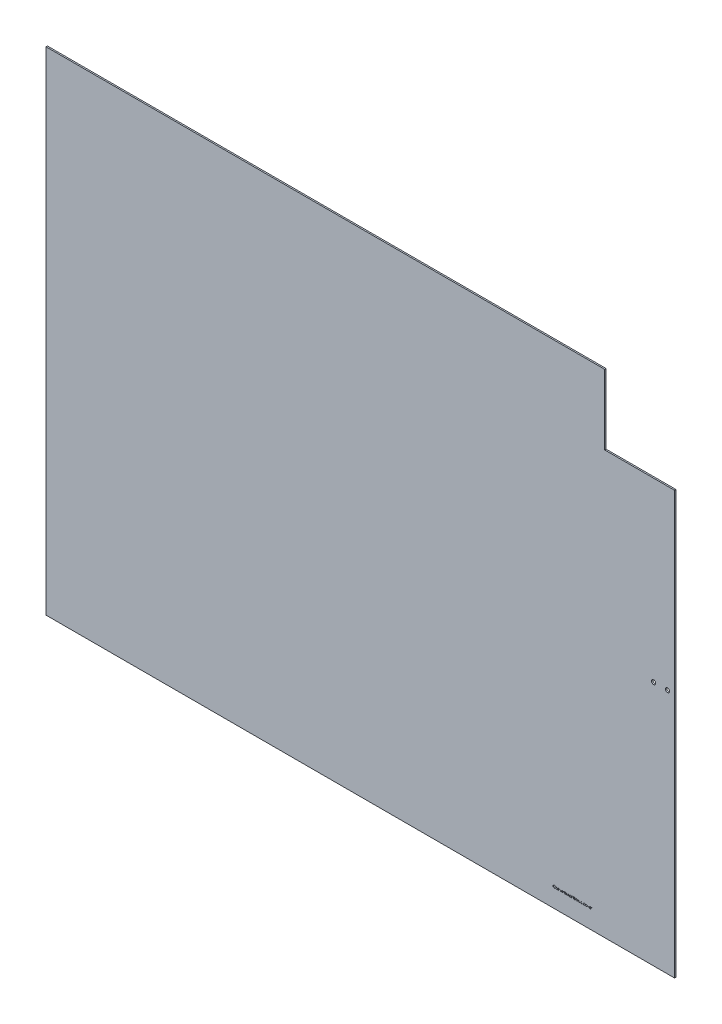
SolidWorks part; units mm, degrees
ref_plane "Front Plane" through (0, 0, 0) normal (0, 0, 1) x (1, 0, 0)
ref_plane "Top Plane" through (0, 0, 0) normal (0, 1, 0) x (1, 0, 0)
ref_plane "Right Plane" through (0, 0, 0) normal (1, 0, 0) x (0, 0, -1)
sketch "Sketch1" plane through (0, 0, 0) normal (0, 0, 1) x (1, 0, 0)
  line L1 (0, 0) -> (900, 0)
  line L2 (0, 0) -> (0, 705)
  line L3 (0, 705) -> (900, 705)
  line L4 (900, 0) -> (900, 705)
  dimension "D1" = 900
  dimension "D2" = 705
extrude "Boss-Extrude1" add sketch "Sketch1" along normal blind 2
sketch "Sketch2" plane through (0, 0, 2) normal (0, 0, 1) x (1, 0, 0)
  line L1 (900, 705) -> (800, 705)
  line L2 (900, 705) -> (900, 605)
  line L3 (900, 605) -> (800, 605)
  line L4 (800, 705) -> (800, 605)
  dimension "D1" = 100
  dimension "D2" = 100
extrude "Cut-Extrude1" cut sketch "Sketch2" against normal through all
sketch "Sketch3" plane through (0, 0, 2) normal (0, 0, 1) x (1, 0, 0)
  line L0 (725.7837, 25.5822) -> (873.0501, 25.5822) construction
  line L1 (729.4632, 28.4399) -> (729.1883, 28.2296)
  line L2 (729.1883, 26.4347) -> (729.4632, 26.2265)
  line L3 (733.2773, 28.1399) -> (733.5914, 28.1399)
  line L4 (733.5914, 28.1399) -> (733.5914, 27.6953)
  line L5 (737.0914, 26.9676) -> (737.0914, 25.5822)
  line L6 (737.0914, 25.5822) -> (736.7773, 25.5822)
  line L7 (736.7773, 25.5822) -> (736.7773, 26.969)
  line L8 (735.3414, 26.5771) -> (735.3414, 25.5822)
  line L9 (735.3414, 25.5822) -> (735.0273, 25.5822)
  line L10 (735.0273, 25.5822) -> (735.0273, 26.8827)
  line L11 (733.5914, 26.6584) -> (733.5914, 25.5822)
  line L12 (733.5914, 25.5822) -> (733.2773, 25.5822)
  line L13 (733.2773, 25.5822) -> (733.2773, 28.1399)
  line L14 (737.8093, 28.1399) -> (738.1234, 28.1399)
  line L15 (738.1234, 28.1399) -> (738.1234, 27.6666)
  line L16 (738.1234, 26.0456) -> (738.1234, 24.6399)
  line L17 (738.1234, 24.6399) -> (737.8093, 24.6399)
  line L18 (737.8093, 24.6399) -> (737.8093, 28.1399)
  line L19 (741.0401, 28.1399) -> (741.3542, 28.1399)
  line L20 (741.3542, 28.1399) -> (741.3542, 27.7633)
  line L21 (742.2516, 28.0971) -> (742.0791, 27.825)
  line L22 (741.3542, 26.4417) -> (741.3542, 25.5822)
  line L23 (741.3542, 25.5822) -> (741.0401, 25.5822)
  line L24 (741.0401, 25.5822) -> (741.0401, 28.1399)
  line L25 (744.6649, 26.3899) -> (744.9439, 26.2433)
  line L26 (745.0785, 26.7937) -> (742.7901, 26.7937)
  line L27 (742.823, 27.1078) -> (744.7644, 27.1078)
  line L28 (746.9183, 27.8208) -> (746.7051, 27.6014)
  line L29 (745.4824, 25.8836) -> (745.6906, 26.1206)
  line L30 (748.8029, 27.8208) -> (748.5898, 27.6014)
  line L31 (747.367, 25.8836) -> (747.5752, 26.1206)
  line L32 (752.5721, 28.1399) -> (752.8862, 28.1399)
  line L33 (752.8862, 28.1399) -> (752.8862, 27.7633)
  line L34 (753.7837, 28.0971) -> (753.6112, 27.825)
  line L35 (752.8862, 26.4417) -> (752.8862, 25.5822)
  line L36 (752.8862, 25.5822) -> (752.5721, 25.5822)
  line L37 (752.5721, 25.5822) -> (752.5721, 28.1399)
  line L38 (755.4439, 25.5822) -> (755.4439, 29.1719)
  line L39 (755.4439, 29.1719) -> (755.758, 29.1719)
  line L40 (755.758, 29.1719) -> (755.758, 27.6757)
  line L41 (755.758, 26.0554) -> (755.758, 25.5822)
  line L42 (755.758, 25.5822) -> (755.4439, 25.5822)
  line L43 (761.367, 28.1399) -> (761.367, 25.5822)
  line L44 (761.367, 25.5822) -> (761.0529, 25.5822)
  line L45 (761.0529, 25.5822) -> (761.0529, 26.0246)
  line L46 (761.0529, 27.6666) -> (761.0529, 28.1399)
  line L47 (761.0529, 28.1399) -> (761.367, 28.1399)
  line L48 (764.5978, 27.5853) -> (764.3348, 27.4219)
  line L49 (764.3348, 26.3001) -> (764.5978, 26.1276)
  line L50 (765.226, 29.1719) -> (765.5401, 29.1719)
  line L51 (765.5401, 29.1719) -> (765.5401, 27.0966)
  line L52 (765.5401, 27.0966) -> (766.7039, 28.1399)
  line L53 (766.7039, 28.1399) -> (767.1555, 28.1399)
  line L54 (767.1555, 28.1399) -> (765.8051, 26.9283)
  line L55 (765.8051, 26.9283) -> (767.2901, 25.5822)
  line L56 (767.2901, 25.5822) -> (766.8393, 25.5822)
  line L57 (766.8393, 25.5822) -> (765.5401, 26.7607)
  line L58 (765.5401, 26.7607) -> (765.5401, 25.5822)
  line L59 (765.5401, 25.5822) -> (765.226, 25.5822)
  line L60 (765.226, 25.5822) -> (765.226, 29.1719)
  line L61 (771.508, 27.5853) -> (771.2451, 27.4219)
  line L62 (771.2451, 26.3001) -> (771.508, 26.1276)
  line L63 (775.0529, 28.1399) -> (775.3929, 28.1399)
  line L64 (775.3929, 28.1399) -> (776.242, 26.2777)
  line L65 (776.242, 26.2777) -> (777.0911, 28.1399)
  line L66 (777.0911, 28.1399) -> (777.4311, 28.1399)
  line L67 (777.4311, 28.1399) -> (776.2644, 25.5822)
  line L68 (776.2644, 25.5822) -> (776.2196, 25.5822)
  line L69 (776.2196, 25.5822) -> (775.0529, 28.1399)
  line L70 (780.0687, 26.3899) -> (780.3478, 26.2433)
  line L71 (780.4824, 26.7937) -> (778.1939, 26.7937)
  line L72 (778.2269, 27.1078) -> (780.1683, 27.1078)
  line L73 (781.0208, 28.1399) -> (781.3349, 28.1399)
  line L74 (781.3349, 28.1399) -> (781.3349, 27.7633)
  line L75 (782.2324, 28.0971) -> (782.0599, 27.825)
  line L76 (781.3349, 26.4417) -> (781.3349, 25.5822)
  line L77 (781.3349, 25.5822) -> (781.0208, 25.5822)
  line L78 (781.0208, 25.5822) -> (781.0208, 28.1399)
  spline S0 degree 3 poles (729.1883, 28.2296) (729.1501, 28.2766) (729.0894, 28.3438) (729.0018, 28.4256) (728.9339, 28.4829) (728.8621, 28.5343) (728.7883, 28.5826) (728.7111, 28.6258) (728.6043, 28.6783) (728.4647, 28.733) (728.2272, 28.7954) (728.0416, 28.8135) (727.9165, 28.8129) knots 0 0 0 0 0.125475 0.187121 0.248294 0.309295 0.36985 0.430973 0.492456 0.616148 0.740844 1 1 1 1
  spline S1 degree 3 poles (727.9165, 28.8129) (727.8466, 28.8138) (727.7426, 28.8063) (727.6062, 28.7862) (727.5065, 28.7641) (727.4089, 28.7361) (727.3128, 28.7027) (727.2196, 28.6613) (727.128, 28.6156) (727.0402, 28.564) (726.9571, 28.5077) (726.8791, 28.4473) (726.8061, 28.3827) (726.7379, 28.314) (726.6751, 28.2406) (726.6179, 28.1628) (726.5652, 28.0815) (726.518, 27.9969) (726.4784, 27.9089) (726.4434, 27.8188) (726.4157, 27.7256) (726.3938, 27.6301) (726.3733, 27.4979) (726.3661, 27.3969) (726.367, 27.3287) knots 0 0 0 0 0.087502 0.130463 0.172752 0.215403 0.25765 0.300153 0.343121 0.385925 0.427686 0.468818 0.509492 0.549883 0.58998 0.630405 0.670869 0.711384 0.751627 0.791776 0.832459 0.873319 0.914543 1 1 1 1
  spline S2 degree 3 poles (726.367, 27.3287) (726.3665, 27.2271) (726.3807, 27.077) (726.4263, 26.8841) (726.4765, 26.7487) (726.5384, 26.6188) (726.6167, 26.4965) (726.7073, 26.3801) (726.8116, 26.2723) (726.926, 26.1738) (727.0487, 26.087) (727.1795, 26.0147) (727.3169, 25.9545) (727.4619, 25.9083) (727.6686, 25.8639) (727.8292, 25.8505) (727.9382, 25.8514) knots 0 0 0 0 0.12629 0.186726 0.246146 0.305576 0.365429 0.426326 0.48884 0.551725 0.613919 0.675484 0.737334 0.800229 0.864502 1 1 1 1
  spline S3 degree 3 poles (727.9382, 25.8514) (728.0584, 25.8514) (728.2369, 25.8683) (728.4648, 25.9303) (728.6261, 25.9941) (728.7794, 26.0772) (728.977, 26.2135) (729.1076, 26.3419) (729.1883, 26.4347) knots 0 0 0 0 0.252949 0.374755 0.49594 0.617181 0.740909 1 1 1 1
  spline S4 degree 3 poles (729.4632, 26.2265) (729.4198, 26.1689) (729.351, 26.0863) (729.2502, 25.9852) (729.1705, 25.9151) (729.0874, 25.849) (728.9993, 25.7887) (728.9075, 25.7334) (728.8121, 25.6827) (728.7134, 25.6378) (728.6114, 25.5994) (728.5065, 25.5662) (728.3989, 25.539) (728.2881, 25.5177) (728.1353, 25.4984) (728.0188, 25.4918) (727.9403, 25.4924) knots 0 0 0 0 0.123053 0.183475 0.243727 0.304279 0.364863 0.425946 0.487391 0.54922 0.611144 0.673529 0.736961 0.800785 0.866013 1 1 1 1
  spline S5 degree 3 poles (727.9403, 25.4924) (727.8658, 25.4915) (727.7558, 25.4975) (727.6113, 25.5131) (727.5076, 25.5303) (727.4064, 25.5506) (727.3089, 25.5779) (727.2139, 25.6084) (727.122, 25.6443) (727.0329, 25.6849) (726.947, 25.7307) (726.8644, 25.7813) (726.7842, 25.8358) (726.7076, 25.8958) (726.6087, 25.9824) (726.5398, 26.0538) (726.4967, 26.1045) knots 0 0 0 0 0.13775 0.203917 0.26878 0.332414 0.394754 0.45618 0.516996 0.577396 0.637198 0.696999 0.756756 0.816554 0.876948 1 1 1 1
  spline S6 degree 3 poles (726.4967, 26.1045) (726.4242, 26.1892) (726.3267, 26.325) (726.2236, 26.5214) (726.1612, 26.6748) (726.1125, 26.8348) (726.0665, 27.0603) (726.0525, 27.2346) (726.0529, 27.3525) knots 0 0 0 0 0.247156 0.36878 0.490734 0.613614 0.738958 1 1 1 1
  spline S7 degree 3 poles (726.0529, 27.3525) (726.0528, 27.4763) (726.0685, 27.6598) (726.1254, 27.8952) (726.1847, 28.0614) (726.26, 28.2206) (726.3531, 28.3714) (726.4627, 28.5149) (726.5882, 28.6489) (726.7257, 28.7715) (726.8731, 28.8793) (727.0298, 28.969) (727.1944, 29.044) (727.3678, 29.1016) (727.6144, 29.1565) (727.8063, 29.1717) (727.9361, 29.1719) knots 0 0 0 0 0.127014 0.187955 0.248014 0.307748 0.368235 0.42947 0.492743 0.556258 0.618217 0.679655 0.741246 0.803415 0.866815 1 1 1 1
  spline S8 degree 3 poles (727.9361, 29.1719) (728.0157, 29.1721) (728.1338, 29.1666) (728.2883, 29.1456) (728.3999, 29.1245) (728.5091, 29.0983) (728.6149, 29.0642) (728.718, 29.0251) (728.8177, 28.9802) (728.9136, 28.9297) (729.0057, 28.8743) (729.0931, 28.814) (729.1766, 28.7493) (729.2547, 28.6789) (729.355, 28.5798) (729.421, 28.4967) (729.4632, 28.4399) knots 0 0 0 0 0.135683 0.201215 0.265682 0.329267 0.392395 0.45507 0.517127 0.57879 0.63974 0.700192 0.759806 0.819628 0.879355 1 1 1 1
  spline S9 degree 3 poles (731.3267, 28.1847) (731.4208, 28.1857) (731.56, 28.1721) (731.7382, 28.1275) (731.864, 28.0823) (731.9823, 28.0216) (732.1347, 27.924) (732.2363, 27.8313) (732.2985, 27.7633) knots 0 0 0 0 0.258332 0.382134 0.503804 0.624693 0.746871 1 1 1 1
  spline S10 degree 3 poles (732.2985, 27.7633) (732.3555, 27.701) (732.4319, 27.6011) (732.5142, 27.4567) (732.5633, 27.3445) (732.6019, 27.2281) (732.6391, 27.0652) (732.6486, 26.9389) (732.649, 26.854) knots 0 0 0 0 0.253834 0.376506 0.498534 0.621368 0.744565 1 1 1 1
  spline S11 degree 3 poles (732.649, 26.854) (732.6496, 26.7684) (732.6378, 26.6413) (732.5992, 26.4769) (732.5584, 26.3591) (732.5061, 26.2452) (732.4422, 26.1358) (732.3663, 26.0306) (732.2803, 25.9306) (732.1852, 25.8384) (732.0821, 25.7581) (731.973, 25.6893) (731.8563, 25.6339) (731.7333, 25.5902) (731.5572, 25.5483) (731.4197, 25.5377) (731.3267, 25.5373) knots 0 0 0 0 0.123337 0.183265 0.243172 0.302898 0.363774 0.425605 0.489659 0.553785 0.616222 0.677854 0.739517 0.802097 0.865866 1 1 1 1
  spline S12 degree 3 poles (731.3267, 25.5373) (731.2333, 25.5377) (731.0953, 25.5482) (730.9188, 25.5902) (730.7956, 25.634) (730.6784, 25.6893) (730.5686, 25.7579) (730.4654, 25.8385) (730.3704, 25.9306) (730.2844, 26.0306) (730.2085, 26.1358) (730.1446, 26.2452) (730.0922, 26.3591) (730.0514, 26.4769) (730.0128, 26.6413) (730.0011, 26.7684) (730.0016, 26.854) knots 0 0 0 0 0.134635 0.198324 0.260825 0.322714 0.384555 0.446913 0.510958 0.574931 0.636685 0.697483 0.757134 0.816966 0.876818 1 1 1 1
  spline S13 degree 3 poles (730.0016, 26.854) (730.0021, 26.9387) (730.0117, 27.0647) (730.0487, 27.2272) (730.0874, 27.3431) (730.1369, 27.4549) (730.2181, 27.5996) (730.2958, 27.6987) (730.3522, 27.7612) knots 0 0 0 0 0.255238 0.378679 0.501088 0.622714 0.746241 1 1 1 1
  spline S14 degree 3 poles (730.3522, 27.7612) (730.4138, 27.8301) (730.5163, 27.9219) (730.6683, 28.0215) (730.788, 28.081) (730.9137, 28.1278) (731.0925, 28.1721) (731.2322, 28.1856) (731.3267, 28.1847) knots 0 0 0 0 0.252713 0.374819 0.496436 0.617911 0.741288 1 1 1 1
  spline S15 degree 3 poles (731.3253, 27.8706) (731.2583, 27.8704) (731.1588, 27.8614) (731.0308, 27.8303) (730.9394, 27.7977) (730.8518, 27.7556) (730.7679, 27.7039) (730.6874, 27.6433) (730.612, 27.5738) (730.5429, 27.4979) (730.4824, 27.4171) (730.431, 27.3326) (730.3881, 27.2443) (730.3562, 27.1514) (730.3248, 27.0212) (730.3159, 26.92) (730.3157, 26.8519) knots 0 0 0 0 0.126044 0.187165 0.247399 0.30838 0.36978 0.432584 0.497641 0.562401 0.625557 0.687332 0.748313 0.809791 0.871768 1 1 1 1
  spline S16 degree 3 poles (730.3157, 26.8519) (730.3159, 26.7632) (730.3315, 26.6299) (730.3899, 26.4619) (730.4484, 26.3423) (730.5218, 26.2316) (730.6083, 26.133) (730.707, 26.0478) (730.8166, 25.9771) (730.9349, 25.921) (731.1033, 25.8671) (731.236, 25.8504) (731.3253, 25.8514) knots 0 0 0 0 0.168179 0.251488 0.335841 0.419834 0.502345 0.583649 0.665931 0.748717 0.831047 1 1 1 1
  spline S17 degree 3 poles (731.3253, 25.8514) (731.4146, 25.8505) (731.5472, 25.8669) (731.7152, 25.9212) (731.8334, 25.977) (731.943, 26.048) (732.0424, 26.1325) (732.1281, 26.2319) (732.2014, 26.3425) (732.2609, 26.4617) (732.319, 26.6299) (732.3348, 26.7632) (732.3349, 26.8519) knots 0 0 0 0 0.168983 0.250908 0.333708 0.416005 0.49766 0.579893 0.663902 0.748466 0.831791 1 1 1 1
  spline S18 degree 3 poles (732.3349, 26.8519) (732.3348, 26.92) (732.3259, 27.0212) (732.2944, 27.1514) (732.2625, 27.2443) (732.2198, 27.3328) (732.1674, 27.4168) (732.1072, 27.4982) (732.0372, 27.5736) (731.9619, 27.6433) (731.8814, 27.7039) (731.7976, 27.7554) (731.7102, 27.7981) (731.6188, 27.83) (731.4912, 27.8616) (731.392, 27.8703) (731.3253, 27.8706) knots 0 0 0 0 0.128274 0.19027 0.251768 0.312769 0.374793 0.43797 0.503047 0.568125 0.63095 0.692369 0.752973 0.813641 0.874355 1 1 1 1
  spline S19 degree 3 poles (733.5914, 27.6953) (733.644, 27.7708) (733.7504, 27.9037) (733.8804, 28.0138) (733.9461, 28.055) knots 0 0 0 0 0.543395 1 1 1 1
  spline S20 degree 3 poles (733.9461, 28.055) (734.0277, 28.0971) (734.1995, 28.1638) (734.3827, 28.184) (734.4734, 28.1847) knots 0 0 0 0 0.503035 1 1 1 1
  spline S21 degree 3 poles (734.4734, 28.1847) (734.5344, 28.1839) (734.6261, 28.1762) (734.7438, 28.1449) (734.8285, 28.1125) (734.9082, 28.0732) (734.9813, 28.0272) (735.0469, 27.9755) (735.105, 27.9158) (735.1573, 27.8465) (735.225, 27.7327) (735.2638, 27.6356) (735.2874, 27.567) knots 0 0 0 0 0.166532 0.248836 0.331246 0.412957 0.490494 0.566156 0.639987 0.716765 0.802144 1 1 1 1
  spline S22 degree 3 poles (735.2874, 27.567) (735.3135, 27.6161) (735.3565, 27.6865) (735.4208, 27.7737) (735.4709, 27.8337) (735.5233, 27.889) (735.5784, 27.9398) (735.6357, 27.9863) (735.7155, 28.0406) (735.8193, 28.0982) (735.9939, 28.1654) (736.1331, 28.1849) (736.2255, 28.1847) knots 0 0 0 0 0.141226 0.209116 0.27484 0.339483 0.402476 0.464942 0.526833 0.647415 0.765562 1 1 1 1
  spline S23 degree 3 poles (736.2255, 28.1847) (736.3091, 28.1841) (736.4342, 28.1704) (736.5884, 28.1124) (736.6939, 28.0542) (736.789, 27.981) (736.8717, 27.8939) (736.9415, 27.7936) (736.9871, 27.6992) (737.018, 27.6159) (737.0371, 27.5449) (737.0539, 27.4667) (737.0679, 27.3813) (737.0781, 27.2884) (737.0886, 27.1498) (737.0917, 27.0419) (737.0914, 26.9676) knots 0 0 0 0 0.147965 0.218797 0.28947 0.359724 0.429708 0.500497 0.574429 0.613947 0.657155 0.703973 0.754939 0.809707 0.868833 1 1 1 1
  spline S24 degree 3 poles (736.7773, 26.969) (736.7773, 27.0318) (736.7764, 27.1222) (736.7693, 27.2371) (736.7633, 27.3113) (736.7551, 27.3775) (736.7444, 27.4357) (736.7332, 27.4863) (736.7144, 27.5424) (736.6845, 27.6043) (736.6389, 27.671) (736.5814, 27.7291) (736.515, 27.7795) (736.4395, 27.8205) (736.3256, 27.8607) (736.2333, 27.871) (736.1708, 27.8706) knots 0 0 0 0 0.150563 0.216151 0.27568 0.328707 0.375904 0.417302 0.452693 0.517265 0.581217 0.645322 0.712024 0.78013 0.850218 1 1 1 1
  spline S25 degree 3 poles (736.1708, 27.8706) (736.0922, 27.872) (735.9752, 27.8527) (735.8283, 27.7947) (735.7261, 27.7323) (735.6321, 27.6575) (735.5512, 27.5686) (735.4843, 27.4679) (735.4391, 27.3748) (735.4105, 27.2911) (735.3916, 27.218) (735.3769, 27.1349) (735.3631, 27.0424) (735.3542, 26.9399) (735.3428, 26.7839) (735.3418, 26.6616) (735.3414, 26.5771) knots 0 0 0 0 0.134707 0.201865 0.270788 0.340024 0.408083 0.476813 0.547346 0.58564 0.628865 0.677153 0.730803 0.789807 0.854325 1 1 1 1
  spline S26 degree 3 poles (735.0273, 26.8827) (735.0273, 26.9533) (735.0264, 27.0546) (735.0193, 27.1833) (735.0134, 27.2662) (735.0049, 27.3396) (734.9953, 27.404) (734.984, 27.4592) (734.9652, 27.5197) (734.9365, 27.5865) (734.8903, 27.6576) (734.8327, 27.7199) (734.7651, 27.773) (734.6891, 27.817) (734.5747, 27.8602) (734.4813, 27.8701) (734.4187, 27.8706) knots 0 0 0 0 0.158779 0.227738 0.289946 0.345499 0.393896 0.436374 0.472122 0.536384 0.599078 0.661948 0.726311 0.791771 0.858647 1 1 1 1
  spline S27 degree 3 poles (734.4187, 27.8706) (734.3429, 27.8713) (734.2289, 27.8531) (734.0861, 27.7955) (733.9842, 27.7359) (733.8905, 27.662) (733.8085, 27.5751) (733.7395, 27.4763) (733.6938, 27.3841) (733.6643, 27.3025) (733.6447, 27.2332) (733.6279, 27.1562) (733.6153, 27.0713) (733.6033, 26.9791) (733.5951, 26.8405) (733.5904, 26.7328) (733.5914, 26.6584) knots 0 0 0 0 0.136871 0.206114 0.277538 0.349772 0.421251 0.492911 0.567027 0.606614 0.649704 0.697303 0.749086 0.804881 0.865485 1 1 1 1
  spline S28 degree 3 poles (738.1234, 27.6666) (738.1856, 27.7519) (738.29, 27.8678) (738.4513, 27.992) (738.5784, 28.0634) (738.7128, 28.1172) (738.9041, 28.1714) (739.0551, 28.1844) (739.1569, 28.1847) knots 0 0 0 0 0.263045 0.386061 0.505771 0.625178 0.746148 1 1 1 1
  spline S29 degree 3 poles (739.1569, 28.1847) (739.2465, 28.1838) (739.3798, 28.1739) (739.5512, 28.1331) (739.6728, 28.0897) (739.79, 28.0361) (739.9013, 27.9684) (740.0082, 27.8899) (740.1081, 27.7997) (740.2004, 27.7021) (740.2803, 27.5971) (740.3491, 27.4881) (740.4048, 27.3735) (740.4484, 27.2542) (740.4904, 27.0864) (740.5011, 26.9558) (740.5016, 26.868) knots 0 0 0 0 0.128636 0.190653 0.252125 0.313446 0.375227 0.438498 0.503285 0.56801 0.630879 0.692154 0.752552 0.813191 0.873985 1 1 1 1
  spline S30 degree 3 poles (740.5016, 26.868) (740.5014, 26.7785) (740.4899, 26.6458) (740.4492, 26.4751) (740.4062, 26.3538) (740.3506, 26.2378) (740.2829, 26.1272) (740.203, 26.022) (740.1117, 25.9237) (740.0126, 25.8331) (739.9067, 25.7538) (739.7957, 25.6873) (739.68, 25.6317) (739.5587, 25.5899) (739.3885, 25.5489) (739.2559, 25.5376) (739.1667, 25.5373) knots 0 0 0 0 0.128034 0.189574 0.25058 0.311733 0.37325 0.435763 0.500346 0.564949 0.627528 0.689157 0.749865 0.81076 0.8723 1 1 1 1
  spline S31 degree 3 poles (739.1667, 25.5373) (739.0662, 25.5361) (738.9177, 25.5533) (738.7274, 25.6059) (738.5932, 25.6625) (738.465, 25.7348) (738.3, 25.8543) (738.1909, 25.9655) (738.1234, 26.0456) knots 0 0 0 0 0.250548 0.37123 0.492116 0.613401 0.737997 1 1 1 1
  spline S32 degree 3 poles (739.1541, 27.8706) (739.084, 27.8717) (738.9805, 27.8616) (738.8469, 27.832) (738.7527, 27.7991) (738.6625, 27.7587) (738.5768, 27.7082) (738.4957, 27.6486) (738.4195, 27.5809) (738.3507, 27.5063) (738.2897, 27.4267) (738.2385, 27.3422) (738.196, 27.2536) (738.1637, 27.1602) (738.1325, 27.028) (738.1236, 26.9249) (738.1234, 26.8554) knots 0 0 0 0 0.130024 0.192374 0.253884 0.314896 0.375806 0.438242 0.501591 0.564881 0.626533 0.687516 0.748106 0.808796 0.870822 1 1 1 1
  spline S33 degree 3 poles (738.1234, 26.8554) (738.1236, 26.7646) (738.1387, 26.6295) (738.1947, 26.4597) (738.2532, 26.3422) (738.3272, 26.2342) (738.4163, 26.1376) (738.5197, 26.0528) (738.6358, 25.9813) (738.7602, 25.9234) (738.9333, 25.8677) (739.0688, 25.8516) (739.159, 25.8514) knots 0 0 0 0 0.169344 0.251061 0.332326 0.413189 0.494299 0.576654 0.661785 0.747765 0.831967 1 1 1 1
  spline S34 degree 3 poles (739.159, 25.8514) (739.2474, 25.8509) (739.3796, 25.8687) (739.5485, 25.9237) (739.6687, 25.9832) (739.7815, 26.0562) (739.8834, 26.1437) (739.9724, 26.2452) (740.0483, 26.3582) (740.1094, 26.4794) (740.1706, 26.6458) (740.1865, 26.7777) (740.1875, 26.8645) knots 0 0 0 0 0.165574 0.248159 0.332033 0.416257 0.499525 0.583039 0.668596 0.754035 0.83692 1 1 1 1
  spline S35 degree 3 poles (740.1875, 26.8645) (740.1887, 26.952) (740.1691, 27.083) (740.1116, 27.2504) (740.0492, 27.3699) (739.9749, 27.4827) (739.8852, 27.5822) (739.7846, 27.6694) (739.6719, 27.7414) (739.551, 27.7987) (739.3799, 27.8552) (739.2446, 27.8702) (739.1541, 27.8706) knots 0 0 0 0 0.163349 0.245826 0.330367 0.415198 0.497941 0.580476 0.66374 0.747513 0.830399 1 1 1 1
  spline S36 degree 3 poles (741.3542, 27.7633) (741.3972, 27.8311) (741.4651, 27.9248) (741.5709, 28.0275) (741.6486, 28.086) (741.729, 28.1298) (741.8365, 28.1725) (741.9221, 28.1843) (741.9782, 28.1847) knots 0 0 0 0 0.306112 0.438367 0.560541 0.675317 0.786114 1 1 1 1
  spline S37 degree 3 poles (741.9782, 28.1847) (742.0232, 28.1844) (742.1196, 28.1675) (742.2073, 28.1239) (742.2516, 28.0971) knots 0 0 0 0 0.463523 1 1 1 1
  spline S38 degree 3 poles (742.0791, 27.825) (742.0505, 27.8377) (741.9991, 27.861) (741.9433, 27.8703) (741.9186, 27.8706) knots 0 0 0 0 0.56023 1 1 1 1
  spline S39 degree 3 poles (741.9186, 27.8706) (741.8671, 27.8707) (741.7882, 27.8518) (741.6932, 27.795) (741.6351, 27.7468) (741.59, 27.7002) (741.5579, 27.6596) (741.5284, 27.614) (741.5002, 27.5643) (741.4746, 27.5095) (741.4417, 27.4285) (741.4222, 27.364) (741.4103, 27.3195) knots 0 0 0 0 0.191338 0.295191 0.410312 0.47193 0.536425 0.603119 0.674118 0.749332 0.828283 1 1 1 1
  spline S40 degree 3 poles (741.4103, 27.3195) (741.3985, 27.2749) (741.3871, 27.1997) (741.3748, 27.09) (741.3677, 26.987) (741.3611, 26.8704) (741.3559, 26.6872) (741.3536, 26.5427) (741.3542, 26.4417) knots 0 0 0 0 0.156938 0.2586 0.375891 0.508166 0.656238 1 1 1 1
  spline S41 degree 3 poles (744.9439, 26.2433) (744.9024, 26.1656) (744.8329, 26.0566) (744.726, 25.9269) (744.6409, 25.8451) (744.5513, 25.7739) (744.4565, 25.7115) (744.3562, 25.6584) (744.2504, 25.6137) (744.1381, 25.5793) (743.9757, 25.546) (743.8488, 25.5373) (743.7625, 25.5373) knots 0 0 0 0 0.181661 0.265874 0.346355 0.4246 0.501903 0.579992 0.658443 0.738672 0.821894 1 1 1 1
  spline S42 degree 3 poles (743.7625, 25.5373) (743.6668, 25.5373) (743.5258, 25.5483) (743.3466, 25.5915) (743.2234, 25.6354) (743.1087, 25.6928) (743.0022, 25.7628) (742.9033, 25.8449) (742.8153, 25.9399) (742.7361, 26.0416) (742.6661, 26.1476) (742.6077, 26.2575) (742.5601, 26.3708) (742.5217, 26.4867) (742.4857, 26.6471) (742.4769, 26.771) (742.476, 26.854) knots 0 0 0 0 0.139629 0.204797 0.268135 0.329814 0.391301 0.453434 0.516552 0.579631 0.641119 0.701294 0.76081 0.819932 0.87892 1 1 1 1
  spline S43 degree 3 poles (742.476, 26.854) (742.4769, 26.9318) (742.4842, 27.0479) (742.5158, 27.1985) (742.548, 27.3073) (742.5896, 27.4129) (742.6577, 27.5504) (742.7229, 27.6465) (742.7704, 27.708) knots 0 0 0 0 0.253768 0.377428 0.500551 0.623296 0.746578 1 1 1 1
  spline S44 degree 3 poles (742.7704, 27.708) (742.831, 27.7837) (742.9298, 27.8896) (743.0844, 28.0003) (743.206, 28.0684) (743.3364, 28.12) (743.5229, 28.1725) (743.6708, 28.1835) (743.7702, 28.1847) knots 0 0 0 0 0.253589 0.374643 0.49534 0.616325 0.739759 1 1 1 1
  spline S45 degree 3 poles (743.7702, 28.1847) (743.8731, 28.1852) (744.025, 28.1703) (744.2176, 28.117) (744.3514, 28.0619) (744.4771, 27.9907) (744.6354, 27.8716) (744.7388, 27.762) (744.8002, 27.6813) knots 0 0 0 0 0.259033 0.38188 0.502258 0.622752 0.744743 1 1 1 1
  spline S46 degree 3 poles (744.8002, 27.6813) (744.8461, 27.6224) (744.906, 27.5268) (744.9696, 27.39) (745.008, 27.2811) (745.039, 27.1673) (745.0696, 27.0049) (745.0769, 26.879) (745.0785, 26.7937) knots 0 0 0 0 0.236255 0.356174 0.47725 0.60154 0.729618 1 1 1 1
  spline S47 degree 3 poles (742.7901, 26.7937) (742.7919, 26.7275) (742.8007, 26.6296) (742.831, 26.5044) (742.8623, 26.4173) (742.9001, 26.3344) (742.9465, 26.2562) (743.0019, 26.1832) (743.0636, 26.1146) (743.1323, 26.0535) (743.2046, 25.9989) (743.2815, 25.9531) (743.3624, 25.9159) (743.4471, 25.8868) (743.5671, 25.8598) (743.6603, 25.851) (743.7233, 25.8514) knots 0 0 0 0 0.134476 0.198391 0.260753 0.321829 0.383037 0.444653 0.507398 0.569825 0.630778 0.690929 0.750945 0.811049 0.872331 1 1 1 1
  spline S48 degree 3 poles (743.7233, 25.8514) (743.7855, 25.8511) (743.8788, 25.8584) (744.0006, 25.8839) (744.0899, 25.9098) (744.1754, 25.9414) (744.2547, 25.9795) (744.3276, 26.0216) (744.3957, 26.0698) (744.4617, 26.1289) (744.5552, 26.2337) (744.6223, 26.3233) (744.6649, 26.3899) knots 0 0 0 0 0.163879 0.245659 0.327726 0.40861 0.485749 0.559169 0.630268 0.705306 0.792065 1 1 1 1
  spline S49 degree 3 poles (744.7644, 27.1078) (744.7446, 27.1885) (744.7049, 27.3025) (744.6325, 27.4394) (744.5709, 27.525) (744.5011, 27.601) (744.4204, 27.6674) (744.33, 27.7268) (744.2302, 27.777) (744.1246, 27.8196) (743.9768, 27.8582) (743.8628, 27.8718) (743.7864, 27.8706) knots 0 0 0 0 0.185231 0.267501 0.3444 0.419595 0.496891 0.576638 0.660268 0.745387 0.83004 1 1 1 1
  spline S50 degree 3 poles (743.7864, 27.8706) (743.7244, 27.8708) (743.6324, 27.8641) (743.5141, 27.8383) (743.4294, 27.8124) (743.3488, 27.7778) (743.2437, 27.7234) (743.1728, 27.6691) (743.1273, 27.6308) knots 0 0 0 0 0.259141 0.384162 0.505992 0.629098 0.750669 1 1 1 1
  spline S51 degree 3 poles (743.1273, 27.6308) (743.0924, 27.6015) (743.0452, 27.5506) (742.9885, 27.4758) (742.9491, 27.4128) (742.9131, 27.3441) (742.8669, 27.2435) (742.8395, 27.1631) (742.823, 27.1078) knots 0 0 0 0 0.22258 0.3385 0.458709 0.585535 0.717518 1 1 1 1
  spline S52 degree 3 poles (746.7051, 27.6014) (746.6703, 27.6429) (746.6169, 27.7009) (746.539, 27.7649) (746.484, 27.8038) (746.4285, 27.8332) (746.3565, 27.8615) (746.3002, 27.8706) (746.2634, 27.8706) knots 0 0 0 0 0.305036 0.441309 0.565963 0.683525 0.793334 1 1 1 1
  spline S53 degree 3 poles (746.2634, 27.8706) (746.2198, 27.8715) (746.1547, 27.8574) (746.0774, 27.8139) (746.0272, 27.768) (745.9847, 27.7152) (745.9431, 27.6363) (745.9312, 27.5703) (745.9311, 27.5264) knots 0 0 0 0 0.245901 0.369166 0.498511 0.628504 0.751028 1 1 1 1
  spline S54 degree 3 poles (745.9311, 27.5264) (745.9312, 27.486) (745.9469, 27.4019) (745.9913, 27.3288) (746.018, 27.2943) knots 0 0 0 0 0.479403 1 1 1 1
  spline S55 degree 3 poles (746.018, 27.2943) (746.034, 27.2726) (746.0652, 27.243) (746.1108, 27.2029) (746.1541, 27.1709) (746.2029, 27.1373) (746.2797, 27.0899) (746.3399, 27.0533) (746.3833, 27.0307) knots 0 0 0 0 0.17756 0.283982 0.402217 0.533568 0.676121 1 1 1 1
  spline S56 degree 3 poles (746.3833, 27.0307) (746.436, 27.0015) (746.5119, 26.9577) (746.6056, 26.8948) (746.667, 26.8502) (746.721, 26.805) (746.7827, 26.7488) (746.8218, 26.703) (746.844, 26.6717) knots 0 0 0 0 0.307115 0.446213 0.574876 0.694152 0.804581 1 1 1 1
  spline S57 degree 3 poles (746.844, 26.6717) (746.882, 26.6142) (746.9461, 26.4875) (746.9622, 26.3465) (746.9632, 26.2763) knots 0 0 0 0 0.495235 1 1 1 1
  spline S58 degree 3 poles (746.9632, 26.2763) (746.9627, 26.2265) (746.9572, 26.1525) (746.9342, 26.0577) (746.9111, 25.99) (746.8799, 25.9261) (746.8434, 25.8642) (746.7995, 25.8059) (746.7494, 25.751) (746.6946, 25.7009) (746.6361, 25.6569) (746.5738, 25.6203) (746.5083, 25.5901) (746.4393, 25.566) (746.3413, 25.5434) (746.265, 25.5376) (746.2137, 25.5373) knots 0 0 0 0 0.127199 0.188597 0.24864 0.309525 0.370037 0.431889 0.495704 0.559519 0.621372 0.682397 0.743568 0.805498 0.86864 1 1 1 1
  spline S59 degree 3 poles (746.2137, 25.5373) (746.1434, 25.5368) (746.0382, 25.5489) (745.9026, 25.5876) (745.8042, 25.6273) (745.7112, 25.6774) (745.598, 25.757) (745.5246, 25.83) (745.4824, 25.8836) knots 0 0 0 0 0.251724 0.377219 0.504694 0.631458 0.755401 1 1 1 1
  spline S60 degree 3 poles (745.6906, 26.1206) (745.7283, 26.0787) (745.7866, 26.02) (745.8724, 25.9565) (745.9352, 25.9179) (745.9995, 25.8882) (746.0859, 25.8602) (746.1531, 25.8512) (746.1975, 25.8514) knots 0 0 0 0 0.285904 0.417172 0.540501 0.659238 0.775006 1 1 1 1
  spline S61 degree 3 poles (746.1975, 25.8514) (746.2567, 25.8509) (746.3446, 25.8662) (746.4503, 25.9179) (746.5183, 25.972) (746.5761, 26.0349) (746.6323, 26.1293) (746.6494, 26.2097) (746.649, 26.2629) knots 0 0 0 0 0.261896 0.387836 0.517686 0.644509 0.764718 1 1 1 1
  spline S62 degree 3 poles (746.649, 26.2629) (746.6489, 26.3069) (746.6349, 26.3952) (746.5907, 26.473) (746.5628, 26.5069) knots 0 0 0 0 0.500453 1 1 1 1
  spline S63 degree 3 poles (746.5628, 26.5069) (746.546, 26.5272) (746.5148, 26.5566) (746.4669, 26.5947) (746.4217, 26.6271) (746.3697, 26.6606) (746.2871, 26.7092) (746.2215, 26.7461) (746.1751, 26.7706) knots 0 0 0 0 0.167462 0.27227 0.389551 0.520801 0.666263 1 1 1 1
  spline S64 degree 3 poles (746.1751, 26.7706) (746.1245, 26.7985) (746.0515, 26.8402) (745.9624, 26.9019) (745.9033, 26.9448) (745.8512, 26.9882) (745.7933, 27.0446) (745.755, 27.0887) (745.7341, 27.1197) knots 0 0 0 0 0.30595 0.443775 0.572824 0.692154 0.802296 1 1 1 1
  spline S65 degree 3 poles (745.7341, 27.1197) (745.6948, 27.1761) (745.6364, 27.304) (745.6157, 27.443) (745.617, 27.5137) knots 0 0 0 0 0.492591 1 1 1 1
  spline S66 degree 3 poles (745.617, 27.5137) (745.6173, 27.5599) (745.6214, 27.6285) (745.6421, 27.7161) (745.6612, 27.7782) (745.6877, 27.8367) (745.7193, 27.8924) (745.7565, 27.9451) (745.7993, 27.9941) (745.8464, 28.0386) (745.8973, 28.0774) (745.9509, 28.1105) (746.0073, 28.1383) (746.0671, 28.1593) (746.1523, 28.179) (746.2185, 28.1853) (746.2634, 28.1847) knots 0 0 0 0 0.133044 0.196507 0.258613 0.319728 0.380873 0.442636 0.505079 0.567881 0.628814 0.68891 0.748765 0.809386 0.870884 1 1 1 1
  spline S67 degree 3 poles (746.2634, 28.1847) (746.3183, 28.1847) (746.4022, 28.173) (746.5101, 28.1345) (746.5924, 28.0943) (746.6742, 28.0422) (746.7877, 27.9554) (746.8677, 27.8781) (746.9183, 27.8208) knots 0 0 0 0 0.213412 0.326127 0.444452 0.569061 0.702712 1 1 1 1
  spline S68 degree 3 poles (748.5898, 27.6014) (748.5549, 27.6429) (748.5015, 27.7009) (748.4236, 27.7649) (748.3686, 27.8038) (748.3131, 27.8332) (748.2411, 27.8615) (748.1849, 27.8706) (748.148, 27.8706) knots 0 0 0 0 0.305036 0.441309 0.565963 0.683525 0.793334 1 1 1 1
  spline S69 degree 3 poles (748.148, 27.8706) (748.1044, 27.8715) (748.0393, 27.8574) (747.962, 27.8139) (747.9118, 27.768) (747.8694, 27.7152) (747.8277, 27.6363) (747.8158, 27.5703) (747.8157, 27.5264) knots 0 0 0 0 0.245901 0.369166 0.498511 0.628504 0.751028 1 1 1 1
  spline S70 degree 3 poles (747.8157, 27.5264) (747.8158, 27.486) (747.8315, 27.4019) (747.876, 27.3288) (747.9027, 27.2943) knots 0 0 0 0 0.479403 1 1 1 1
  spline S71 degree 3 poles (747.9027, 27.2943) (747.9186, 27.2726) (747.9498, 27.243) (747.9954, 27.2029) (748.0387, 27.1709) (748.0875, 27.1373) (748.1643, 27.0899) (748.2245, 27.0533) (748.2679, 27.0307) knots 0 0 0 0 0.17756 0.283982 0.402217 0.533568 0.676121 1 1 1 1
  spline S72 degree 3 poles (748.2679, 27.0307) (748.3207, 27.0015) (748.3965, 26.9577) (748.4902, 26.8948) (748.5517, 26.8502) (748.6056, 26.805) (748.6673, 26.7488) (748.7064, 26.703) (748.7286, 26.6717) knots 0 0 0 0 0.307115 0.446213 0.574876 0.694152 0.804581 1 1 1 1
  spline S73 degree 3 poles (748.7286, 26.6717) (748.7666, 26.6142) (748.8307, 26.4875) (748.8468, 26.3465) (748.8478, 26.2763) knots 0 0 0 0 0.495235 1 1 1 1
  spline S74 degree 3 poles (748.8478, 26.2763) (748.8473, 26.2265) (748.8418, 26.1525) (748.8188, 26.0577) (748.7957, 25.99) (748.7645, 25.9261) (748.728, 25.8642) (748.6841, 25.8059) (748.634, 25.751) (748.5792, 25.7009) (748.5207, 25.6569) (748.4584, 25.6203) (748.3929, 25.5901) (748.3239, 25.566) (748.226, 25.5434) (748.1497, 25.5376) (748.0983, 25.5373) knots 0 0 0 0 0.127199 0.188597 0.24864 0.309525 0.370037 0.431889 0.495704 0.559519 0.621372 0.682397 0.743568 0.805498 0.86864 1 1 1 1
  spline S75 degree 3 poles (748.0983, 25.5373) (748.028, 25.5368) (747.9228, 25.5489) (747.7872, 25.5876) (747.6889, 25.6273) (747.5958, 25.6774) (747.4826, 25.757) (747.4093, 25.83) (747.367, 25.8836) knots 0 0 0 0 0.251724 0.377219 0.504694 0.631458 0.755401 1 1 1 1
  spline S76 degree 3 poles (747.5752, 26.1206) (747.6129, 26.0787) (747.6712, 26.02) (747.757, 25.9565) (747.8198, 25.9179) (747.8841, 25.8882) (747.9705, 25.8602) (748.0377, 25.8512) (748.0821, 25.8514) knots 0 0 0 0 0.285904 0.417172 0.540501 0.659238 0.775006 1 1 1 1
  spline S77 degree 3 poles (748.0821, 25.8514) (748.1413, 25.8509) (748.2292, 25.8662) (748.3349, 25.9179) (748.4029, 25.972) (748.4607, 26.0349) (748.5169, 26.1293) (748.534, 26.2097) (748.5337, 26.2629) knots 0 0 0 0 0.261896 0.387836 0.517686 0.644509 0.764718 1 1 1 1
  spline S78 degree 3 poles (748.5337, 26.2629) (748.5335, 26.3069) (748.5195, 26.3952) (748.4753, 26.473) (748.4474, 26.5069) knots 0 0 0 0 0.500453 1 1 1 1
  spline S79 degree 3 poles (748.4474, 26.5069) (748.4306, 26.5272) (748.3994, 26.5566) (748.3515, 26.5947) (748.3064, 26.6271) (748.2544, 26.6606) (748.1717, 26.7092) (748.1061, 26.7461) (748.0597, 26.7706) knots 0 0 0 0 0.167462 0.27227 0.389551 0.520801 0.666263 1 1 1 1
  spline S80 degree 3 poles (748.0597, 26.7706) (748.0091, 26.7985) (747.9361, 26.8402) (747.8471, 26.9019) (747.7879, 26.9448) (747.7358, 26.9882) (747.6779, 27.0446) (747.6396, 27.0887) (747.6187, 27.1197) knots 0 0 0 0 0.30595 0.443775 0.572824 0.692154 0.802296 1 1 1 1
  spline S81 degree 3 poles (747.6187, 27.1197) (747.5794, 27.1761) (747.5211, 27.304) (747.5003, 27.443) (747.5016, 27.5137) knots 0 0 0 0 0.492591 1 1 1 1
  spline S82 degree 3 poles (747.5016, 27.5137) (747.5019, 27.5599) (747.5061, 27.6285) (747.5267, 27.7161) (747.5458, 27.7782) (747.5723, 27.8367) (747.6039, 27.8924) (747.6411, 27.9451) (747.6839, 27.9941) (747.731, 28.0386) (747.7819, 28.0774) (747.8355, 28.1105) (747.8919, 28.1383) (747.9517, 28.1593) (748.0369, 28.179) (748.1031, 28.1853) (748.148, 28.1847) knots 0 0 0 0 0.133044 0.196507 0.258613 0.319728 0.380873 0.442636 0.505079 0.567881 0.628814 0.68891 0.748765 0.809386 0.870884 1 1 1 1
  spline S83 degree 3 poles (748.148, 28.1847) (748.2029, 28.1847) (748.2868, 28.173) (748.3947, 28.1345) (748.477, 28.0943) (748.5588, 28.0422) (748.6723, 27.9554) (748.7523, 27.8781) (748.8029, 27.8208) knots 0 0 0 0 0.213412 0.326127 0.444452 0.569061 0.702712 1 1 1 1
  spline S84 degree 3 poles (750.7113, 28.1847) (750.8054, 28.1857) (750.9447, 28.1721) (751.1228, 28.1275) (751.2486, 28.0823) (751.367, 28.0216) (751.5193, 27.924) (751.6209, 27.8313) (751.6831, 27.7633) knots 0 0 0 0 0.258332 0.382134 0.503804 0.624693 0.746871 1 1 1 1
  spline S85 degree 3 poles (751.6831, 27.7633) (751.7401, 27.701) (751.8165, 27.6011) (751.8988, 27.4567) (751.9479, 27.3445) (751.9865, 27.2281) (752.0237, 27.0652) (752.0332, 26.9389) (752.0337, 26.854) knots 0 0 0 0 0.253834 0.376506 0.498534 0.621368 0.744565 1 1 1 1
  spline S86 degree 3 poles (752.0337, 26.854) (752.0342, 26.7684) (752.0225, 26.6413) (751.9838, 26.4769) (751.943, 26.3591) (751.8907, 26.2452) (751.8268, 26.1358) (751.7509, 26.0306) (751.6649, 25.9306) (751.5699, 25.8384) (751.4667, 25.7581) (751.3576, 25.6893) (751.2409, 25.6339) (751.1179, 25.5902) (750.9418, 25.5483) (750.8043, 25.5377) (750.7113, 25.5373) knots 0 0 0 0 0.123337 0.183265 0.243172 0.302898 0.363774 0.425605 0.489659 0.553785 0.616222 0.677854 0.739517 0.802097 0.865866 1 1 1 1
  spline S87 degree 3 poles (750.7113, 25.5373) (750.6179, 25.5377) (750.4799, 25.5482) (750.3034, 25.5902) (750.1802, 25.634) (750.063, 25.6893) (749.9532, 25.7579) (749.85, 25.8385) (749.755, 25.9306) (749.669, 26.0306) (749.5931, 26.1358) (749.5292, 26.2452) (749.4768, 26.3591) (749.4361, 26.4769) (749.3974, 26.6413) (749.3857, 26.7684) (749.3862, 26.854) knots 0 0 0 0 0.134635 0.198324 0.260825 0.322714 0.384555 0.446913 0.510958 0.574931 0.636685 0.697483 0.757134 0.816966 0.876818 1 1 1 1
  spline S88 degree 3 poles (749.3862, 26.854) (749.3867, 26.9387) (749.3963, 27.0647) (749.4333, 27.2272) (749.472, 27.3431) (749.5215, 27.4549) (749.6027, 27.5996) (749.6804, 27.6987) (749.7368, 27.7612) knots 0 0 0 0 0.255238 0.378679 0.501088 0.622714 0.746241 1 1 1 1
  spline S89 degree 3 poles (749.7368, 27.7612) (749.7984, 27.8301) (749.9009, 27.9219) (750.0529, 28.0215) (750.1726, 28.081) (750.2983, 28.1278) (750.4772, 28.1721) (750.6168, 28.1856) (750.7113, 28.1847) knots 0 0 0 0 0.252713 0.374819 0.496436 0.617911 0.741288 1 1 1 1
  spline S90 degree 3 poles (750.7099, 27.8706) (750.643, 27.8704) (750.5434, 27.8614) (750.4154, 27.8303) (750.324, 27.7977) (750.2364, 27.7556) (750.1525, 27.7039) (750.072, 27.6433) (749.9967, 27.5738) (749.9275, 27.4979) (749.867, 27.4171) (749.8156, 27.3326) (749.7727, 27.2443) (749.7408, 27.1514) (749.7094, 27.0212) (749.7005, 26.92) (749.7003, 26.8519) knots 0 0 0 0 0.126044 0.187165 0.247399 0.30838 0.36978 0.432584 0.497641 0.562401 0.625557 0.687332 0.748313 0.809791 0.871768 1 1 1 1
  spline S91 degree 3 poles (749.7003, 26.8519) (749.7005, 26.7632) (749.7162, 26.6299) (749.7745, 26.4619) (749.833, 26.3423) (749.9064, 26.2316) (749.9929, 26.133) (750.0916, 26.0478) (750.2012, 25.9771) (750.3195, 25.921) (750.4879, 25.8671) (750.6206, 25.8504) (750.7099, 25.8514) knots 0 0 0 0 0.168179 0.251488 0.335841 0.419834 0.502345 0.583649 0.665931 0.748717 0.831047 1 1 1 1
  spline S92 degree 3 poles (750.7099, 25.8514) (750.7992, 25.8505) (750.9318, 25.8669) (751.0998, 25.9212) (751.2181, 25.977) (751.3276, 26.048) (751.427, 26.1325) (751.5127, 26.2319) (751.5861, 26.3425) (751.6455, 26.4617) (751.7036, 26.6299) (751.7194, 26.7632) (751.7196, 26.8519) knots 0 0 0 0 0.168983 0.250908 0.333708 0.416005 0.49766 0.579893 0.663902 0.748466 0.831791 1 1 1 1
  spline S93 degree 3 poles (751.7196, 26.8519) (751.7194, 26.92) (751.7105, 27.0212) (751.6791, 27.1514) (751.6471, 27.2443) (751.6045, 27.3328) (751.552, 27.4168) (751.4918, 27.4982) (751.4218, 27.5736) (751.3465, 27.6433) (751.266, 27.7039) (751.1822, 27.7554) (751.0949, 27.7981) (751.0034, 27.83) (750.8758, 27.8616) (750.7767, 27.8703) (750.7099, 27.8706) knots 0 0 0 0 0.128274 0.19027 0.251768 0.312769 0.374793 0.43797 0.503047 0.568125 0.63095 0.692369 0.752973 0.813641 0.874355 1 1 1 1
  spline S94 degree 3 poles (752.8862, 27.7633) (752.9292, 27.8311) (752.9972, 27.9248) (753.103, 28.0275) (753.1806, 28.086) (753.261, 28.1298) (753.3686, 28.1725) (753.4541, 28.1843) (753.5102, 28.1847) knots 0 0 0 0 0.306112 0.438367 0.560541 0.675317 0.786114 1 1 1 1
  spline S95 degree 3 poles (753.5102, 28.1847) (753.5552, 28.1844) (753.6517, 28.1675) (753.7393, 28.1239) (753.7837, 28.0971) knots 0 0 0 0 0.463523 1 1 1 1
  spline S96 degree 3 poles (753.6112, 27.825) (753.5826, 27.8377) (753.5311, 27.861) (753.4753, 27.8703) (753.4506, 27.8706) knots 0 0 0 0 0.56023 1 1 1 1
  spline S97 degree 3 poles (753.4506, 27.8706) (753.3991, 27.8707) (753.3202, 27.8518) (753.2253, 27.795) (753.1671, 27.7468) (753.1221, 27.7002) (753.0899, 27.6596) (753.0604, 27.614) (753.0323, 27.5643) (753.0066, 27.5095) (752.9738, 27.4285) (752.9542, 27.364) (752.9423, 27.3195) knots 0 0 0 0 0.191338 0.295191 0.410312 0.47193 0.536425 0.603119 0.674118 0.749332 0.828283 1 1 1 1
  spline S98 degree 3 poles (752.9423, 27.3195) (752.9306, 27.2749) (752.9191, 27.1997) (752.9069, 27.09) (752.8997, 26.987) (752.8932, 26.8704) (752.8879, 26.6872) (752.8857, 26.5427) (752.8862, 26.4417) knots 0 0 0 0 0.156938 0.2586 0.375891 0.508166 0.656238 1 1 1 1
  spline S99 degree 3 poles (755.758, 27.6757) (755.8249, 27.7569) (755.9343, 27.8683) (756.0997, 27.9879) (756.2276, 28.0605) (756.3623, 28.1157) (756.5519, 28.1705) (756.7011, 28.1848) (756.8013, 28.1847) knots 0 0 0 0 0.262681 0.38719 0.50839 0.628966 0.749723 1 1 1 1
  spline S100 degree 3 poles (756.8013, 28.1847) (756.8905, 28.1844) (757.0231, 28.1731) (757.1934, 28.1321) (757.3146, 28.0903) (757.4303, 28.0347) (757.5414, 27.9682) (757.6472, 27.8889) (757.7463, 27.7983) (757.8376, 27.7) (757.9175, 27.5948) (757.985, 27.4843) (758.0408, 27.3689) (758.084, 27.2481) (758.1244, 27.0778) (758.1362, 26.9454) (758.1362, 26.8561) knots 0 0 0 0 0.127821 0.189419 0.250372 0.311137 0.372825 0.435463 0.500128 0.564773 0.627344 0.688919 0.749829 0.810578 0.872176 1 1 1 1
  spline S101 degree 3 poles (758.1362, 26.8561) (758.1359, 26.768) (758.1248, 26.637) (758.0832, 26.4687) (758.0392, 26.3491) (757.984, 26.234) (757.9148, 26.125) (757.835, 26.0199) (757.7427, 25.9223) (757.6428, 25.8321) (757.5359, 25.7537) (757.4247, 25.6859) (757.3074, 25.6323) (757.1858, 25.5889) (757.0144, 25.5481) (756.8811, 25.5382) (756.7915, 25.5373) knots 0 0 0 0 0.126228 0.187289 0.247869 0.308511 0.369727 0.432536 0.497198 0.561923 0.625133 0.686855 0.748117 0.80953 0.871487 1 1 1 1
  spline S102 degree 3 poles (756.7915, 25.5373) (756.6898, 25.5376) (756.5387, 25.5506) (756.3475, 25.6049) (756.2128, 25.6584) (756.0864, 25.7309) (755.924, 25.8535) (755.8212, 25.9712) (755.758, 26.0554) knots 0 0 0 0 0.25388 0.374863 0.494283 0.614293 0.73697 1 1 1 1
  spline S103 degree 3 poles (756.7887, 25.8514) (756.8792, 25.8518) (757.0145, 25.8668) (757.1856, 25.9234) (757.3065, 25.9806) (757.4192, 26.0526) (757.5198, 26.1398) (757.6093, 26.2393) (757.684, 26.3515) (757.7462, 26.4709) (757.8037, 26.6381) (757.8235, 26.7688) (757.8221, 26.8561) knots 0 0 0 0 0.169736 0.252687 0.336526 0.419856 0.502457 0.585265 0.6698 0.754407 0.83695 1 1 1 1
  spline S104 degree 3 poles (757.8221, 26.8561) (757.821, 26.9434) (757.8055, 27.0758) (757.744, 27.2426) (757.6829, 27.3638) (757.607, 27.4768) (757.518, 27.5783) (757.4162, 27.6658) (757.3033, 27.7388) (757.1832, 27.7983) (757.0142, 27.8533) (756.8821, 27.8712) (756.7936, 27.8706) knots 0 0 0 0 0.163805 0.246618 0.331983 0.417466 0.500907 0.584103 0.668254 0.752056 0.83457 1 1 1 1
  spline S105 degree 3 poles (756.7936, 27.8706) (756.7033, 27.8712) (756.5681, 27.8532) (756.3946, 27.7981) (756.2703, 27.7392) (756.1545, 27.6671) (756.0509, 27.5824) (755.9616, 27.4856) (755.888, 27.3771) (755.8296, 27.2599) (755.7729, 27.091) (755.7585, 26.9564) (755.758, 26.8659) knots 0 0 0 0 0.168182 0.252419 0.338618 0.424014 0.506402 0.587545 0.668801 0.7501 0.831022 1 1 1 1
  spline S106 degree 3 poles (755.758, 26.8659) (755.7582, 26.7964) (755.7671, 26.6933) (755.7983, 26.5612) (755.8306, 26.4677) (755.8731, 26.3791) (755.9243, 26.2946) (755.9853, 26.215) (756.0542, 26.1405) (756.1301, 26.0727) (756.2117, 26.0139) (756.2971, 25.9633) (756.3874, 25.9229) (756.4815, 25.89) (756.6151, 25.8604) (756.7186, 25.8504) (756.7887, 25.8514) knots 0 0 0 0 0.129212 0.191253 0.251958 0.312564 0.373562 0.43523 0.498536 0.561901 0.624098 0.685023 0.746051 0.807577 0.869943 1 1 1 1
  spline S107 degree 3 poles (761.0529, 26.0246) (760.9857, 25.9451) (760.8771, 25.8346) (760.7105, 25.72) (760.5819, 25.6518) (760.4469, 25.6006) (760.2569, 25.5512) (760.1085, 25.5365) (760.0082, 25.5373) knots 0 0 0 0 0.262085 0.38627 0.507165 0.6273 0.748145 1 1 1 1
  spline S108 degree 3 poles (760.0082, 25.5373) (759.9192, 25.5375) (759.7869, 25.549) (759.6169, 25.5899) (759.4956, 25.6317) (759.3799, 25.6873) (759.2689, 25.7538) (759.163, 25.8331) (759.0639, 25.9237) (758.9727, 26.0221) (758.8926, 26.127) (758.8259, 26.2381) (758.77, 26.3538) (758.7271, 26.4751) (758.6864, 26.6458) (758.6749, 26.7785) (758.6747, 26.868) knots 0 0 0 0 0.127433 0.189004 0.24993 0.310668 0.372329 0.434939 0.499576 0.564191 0.626735 0.688109 0.749294 0.810331 0.871901 1 1 1 1
  spline S109 degree 3 poles (758.6747, 26.868) (758.6752, 26.9558) (758.6859, 27.0864) (758.7279, 27.2542) (758.7714, 27.3735) (758.8273, 27.4879) (758.8952, 27.5973) (758.9752, 27.702) (759.0675, 27.7997) (759.1674, 27.8899) (759.2743, 27.9684) (759.3856, 28.0361) (759.5028, 28.0897) (759.6244, 28.1331) (759.7956, 28.1738) (759.9286, 28.1839) (760.018, 28.1847) knots 0 0 0 0 0.126079 0.186904 0.247574 0.308003 0.369132 0.432033 0.496791 0.561611 0.624914 0.686726 0.748079 0.809582 0.871631 1 1 1 1
  spline S110 degree 3 poles (760.018, 28.1847) (760.1202, 28.1844) (760.272, 28.1713) (760.464, 28.1173) (760.5986, 28.0635) (760.7258, 27.9918) (760.8877, 27.8686) (760.991, 27.7516) (761.0529, 27.6666) knots 0 0 0 0 0.254654 0.376015 0.495255 0.614798 0.738106 1 1 1 1
  spline S111 degree 3 poles (760.0222, 27.8706) (759.9317, 27.8702) (759.7964, 27.8552) (759.6253, 27.7987) (759.5044, 27.7414) (759.3917, 27.6694) (759.291, 27.5823) (759.2015, 27.4824) (759.1262, 27.3703) (759.0649, 27.2502) (759.007, 27.083) (758.9876, 26.952) (758.9888, 26.8645) knots 0 0 0 0 0.169593 0.252476 0.336244 0.419505 0.502036 0.584775 0.669846 0.754185 0.836658 1 1 1 1
  spline S112 degree 3 poles (758.9888, 26.8645) (758.9895, 26.7776) (759.0062, 26.6461) (759.0661, 26.4793) (759.1272, 26.358) (759.2039, 26.2454) (759.2928, 26.1437) (759.3948, 26.0562) (759.5077, 25.9829) (759.6283, 25.9239) (759.7978, 25.8685) (759.9305, 25.851) (760.0194, 25.8514) knots 0 0 0 0 0.162859 0.245484 0.330807 0.416493 0.499893 0.583048 0.667158 0.751312 0.833785 1 1 1 1
  spline S113 degree 3 poles (760.0194, 25.8514) (760.1098, 25.8518) (760.2454, 25.8674) (760.4182, 25.9235) (760.542, 25.9813) (760.6573, 26.0531) (760.7608, 26.1371) (760.8483, 26.2348) (760.9225, 26.3421) (760.9807, 26.4599) (761.0382, 26.6292) (761.0524, 26.7647) (761.0529, 26.8554) knots 0 0 0 0 0.168664 0.252552 0.33824 0.423103 0.505556 0.586176 0.667136 0.748499 0.830452 1 1 1 1
  spline S114 degree 3 poles (761.0529, 26.8554) (761.0527, 26.9249) (761.0438, 27.028) (761.0126, 27.1602) (760.9803, 27.2536) (760.9378, 27.3422) (760.8866, 27.4267) (760.8257, 27.5065) (760.7561, 27.5807) (760.6799, 27.6483) (760.5993, 27.7087) (760.5133, 27.7583) (760.4234, 27.7993) (760.3294, 27.8319) (760.1958, 27.8616) (760.0923, 27.8716) (760.0222, 27.8706) knots 0 0 0 0 0.129188 0.191219 0.251913 0.312507 0.373494 0.435152 0.498741 0.562095 0.624187 0.685476 0.746097 0.807612 0.869967 1 1 1 1
  spline S115 degree 3 poles (764.3348, 27.4219) (764.2806, 27.4943) (764.1879, 27.5919) (764.0457, 27.6974) (763.9325, 27.7612) (763.8111, 27.8103) (763.6356, 27.8579) (763.4973, 27.8708) (763.4038, 27.8706) knots 0 0 0 0 0.252584 0.373506 0.493364 0.614609 0.73847 1 1 1 1
  spline S116 degree 3 poles (763.4038, 27.8706) (763.3283, 27.8695) (763.2164, 27.8629) (763.0733, 27.8308) (762.9723, 27.7997) (762.8765, 27.7579) (762.7859, 27.7071) (762.6995, 27.6481) (762.6199, 27.5797) (762.5471, 27.5053) (762.484, 27.4255) (762.429, 27.3428) (762.3859, 27.255) (762.3507, 27.1643) (762.3192, 27.0355) (762.309, 26.9356) (762.3093, 26.868) knots 0 0 0 0 0.136921 0.201969 0.265462 0.328248 0.390817 0.45355 0.517542 0.580738 0.641922 0.701597 0.760313 0.818757 0.877718 1 1 1 1
  spline S117 degree 3 poles (762.3093, 26.868) (762.3095, 26.7792) (762.3269, 26.6453) (762.3877, 26.4761) (762.4497, 26.3544) (762.5282, 26.2418) (762.6204, 26.1409) (762.7263, 26.0535) (762.845, 25.981) (762.9738, 25.9228) (763.1597, 25.8663) (763.3068, 25.8518) (763.4059, 25.8514) knots 0 0 0 0 0.159965 0.240321 0.322529 0.405024 0.486597 0.567865 0.651333 0.736238 0.821529 1 1 1 1
  spline S118 degree 3 poles (763.4059, 25.8514) (763.4969, 25.8514) (763.6318, 25.8641) (763.8033, 25.9121) (763.9237, 25.9611) (764.0374, 26.0247) (764.1818, 26.1307) (764.2776, 26.228) (764.3348, 26.3001) knots 0 0 0 0 0.255447 0.377298 0.498442 0.619372 0.741857 1 1 1 1
  spline S119 degree 3 poles (764.5978, 26.1276) (764.5674, 26.0814) (764.518, 26.0148) (764.4429, 25.9343) (764.3829, 25.8781) (764.3198, 25.8249) (764.2515, 25.777) (764.1801, 25.7319) (764.1049, 25.6913) (764.0265, 25.6548) (763.9452, 25.6234) (763.8612, 25.5964) (763.7745, 25.575) (763.6849, 25.5579) (763.5603, 25.5424) (763.4652, 25.5363) (763.401, 25.5373) knots 0 0 0 0 0.119069 0.178197 0.236957 0.295932 0.355856 0.416473 0.477742 0.539903 0.602538 0.665422 0.729765 0.794829 0.861827 1 1 1 1
  spline S120 degree 3 poles (763.401, 25.5373) (763.3037, 25.5363) (763.1603, 25.5486) (762.9758, 25.5881) (762.8461, 25.6296) (762.7228, 25.6832) (762.6059, 25.7485) (762.4959, 25.8263) (762.3938, 25.915) (762.3, 26.0113) (762.2195, 26.1151) (762.1496, 26.2228) (762.0935, 26.3366) (762.0489, 26.455) (762.0075, 26.6223) (761.9949, 26.7522) (761.9952, 26.84) knots 0 0 0 0 0.136335 0.201096 0.26445 0.327005 0.389391 0.451976 0.51567 0.578973 0.640167 0.69974 0.758685 0.81782 0.876984 1 1 1 1
  spline S121 degree 3 poles (761.9952, 26.84) (761.9943, 26.9001) (762.002, 26.9894) (762.0196, 27.1072) (762.0416, 27.1928) (762.067, 27.2774) (762.0995, 27.36) (762.1376, 27.4409) (762.1809, 27.52) (762.2296, 27.596) (762.2834, 27.6677) (762.3405, 27.7361) (762.4034, 27.7989) (762.4694, 27.8584) (762.5405, 27.9132) (762.6162, 27.9633) (762.6954, 28.0098) (762.778, 28.0511) (762.8635, 28.0867) (762.9515, 28.1172) (763.0421, 28.1413) (763.1346, 28.1615) (763.263, 28.1788) (763.3608, 28.1851) (763.4269, 28.1847) knots 0 0 0 0 0.082136 0.122636 0.162831 0.203007 0.243526 0.284173 0.32541 0.366855 0.407551 0.448187 0.488683 0.529015 0.569843 0.61137 0.653238 0.695446 0.737751 0.780043 0.822807 0.865978 0.909595 1 1 1 1
  spline S122 degree 3 poles (763.4269, 28.1847) (763.5105, 28.185) (763.6351, 28.1745) (763.7984, 28.1431) (763.9165, 28.1086) (764.0293, 28.0667) (764.1348, 28.0197) (764.2306, 27.9651) (764.3186, 27.9054) (764.3987, 27.838) (764.4978, 27.7358) (764.5611, 27.6481) (764.5978, 27.5853) knots 0 0 0 0 0.182081 0.27191 0.362049 0.450066 0.533976 0.613602 0.690198 0.765413 0.841437 1 1 1 1
  spline S123 degree 3 poles (771.2451, 27.4219) (771.1908, 27.4943) (771.0981, 27.5919) (770.9559, 27.6974) (770.8427, 27.7612) (770.7213, 27.8103) (770.5459, 27.8579) (770.4076, 27.8708) (770.314, 27.8706) knots 0 0 0 0 0.252584 0.373506 0.493364 0.614609 0.73847 1 1 1 1
  spline S124 degree 3 poles (770.314, 27.8706) (770.2386, 27.8695) (770.1267, 27.8629) (769.9836, 27.8308) (769.8825, 27.7997) (769.7868, 27.7579) (769.6961, 27.7071) (769.6098, 27.6481) (769.5301, 27.5797) (769.4573, 27.5053) (769.3942, 27.4255) (769.3393, 27.3428) (769.2962, 27.255) (769.2609, 27.1643) (769.2294, 27.0355) (769.2192, 26.9356) (769.2196, 26.868) knots 0 0 0 0 0.136921 0.201969 0.265462 0.328248 0.390817 0.45355 0.517542 0.580738 0.641922 0.701597 0.760313 0.818757 0.877718 1 1 1 1
  spline S125 degree 3 poles (769.2196, 26.868) (769.2198, 26.7792) (769.2372, 26.6453) (769.298, 26.4761) (769.36, 26.3544) (769.4385, 26.2418) (769.5306, 26.1409) (769.6365, 26.0535) (769.7553, 25.981) (769.884, 25.9228) (770.07, 25.8663) (770.217, 25.8518) (770.3161, 25.8514) knots 0 0 0 0 0.159965 0.240321 0.322529 0.405024 0.486597 0.567865 0.651333 0.736238 0.821529 1 1 1 1
  spline S126 degree 3 poles (770.3161, 25.8514) (770.4071, 25.8514) (770.542, 25.8641) (770.7135, 25.9121) (770.8339, 25.9611) (770.9476, 26.0247) (771.0921, 26.1307) (771.1879, 26.228) (771.2451, 26.3001) knots 0 0 0 0 0.255447 0.377298 0.498442 0.619372 0.741857 1 1 1 1
  spline S127 degree 3 poles (771.508, 26.1276) (771.4777, 26.0814) (771.4282, 26.0148) (771.3532, 25.9343) (771.2932, 25.8781) (771.2301, 25.8249) (771.1618, 25.777) (771.0904, 25.7319) (771.0151, 25.6913) (770.9368, 25.6548) (770.8554, 25.6234) (770.7715, 25.5964) (770.6848, 25.575) (770.5951, 25.5579) (770.4706, 25.5424) (770.3754, 25.5363) (770.3112, 25.5373) knots 0 0 0 0 0.119069 0.178197 0.236957 0.295932 0.355856 0.416473 0.477742 0.539903 0.602538 0.665422 0.729765 0.794829 0.861827 1 1 1 1
  spline S128 degree 3 poles (770.3112, 25.5373) (770.214, 25.5363) (770.0706, 25.5486) (769.886, 25.5881) (769.7564, 25.6296) (769.633, 25.6832) (769.5162, 25.7485) (769.4061, 25.8263) (769.304, 25.915) (769.2102, 26.0113) (769.1297, 26.1151) (769.0599, 26.2228) (769.0038, 26.3366) (768.9592, 26.455) (768.9178, 26.6223) (768.9052, 26.7522) (768.9055, 26.84) knots 0 0 0 0 0.136335 0.201096 0.26445 0.327005 0.389391 0.451976 0.51567 0.578973 0.640167 0.69974 0.758685 0.81782 0.876984 1 1 1 1
  spline S129 degree 3 poles (768.9055, 26.84) (768.9046, 26.9001) (768.9123, 26.9894) (768.9299, 27.1072) (768.9519, 27.1928) (768.9773, 27.2774) (769.0098, 27.36) (769.0479, 27.4409) (769.0911, 27.52) (769.1398, 27.596) (769.1937, 27.6677) (769.2507, 27.7361) (769.3136, 27.7989) (769.3797, 27.8584) (769.4507, 27.9132) (769.5264, 27.9633) (769.6056, 28.0098) (769.6882, 28.0511) (769.7738, 28.0867) (769.8618, 28.1172) (769.9524, 28.1413) (770.0449, 28.1615) (770.1733, 28.1788) (770.2711, 28.1851) (770.3371, 28.1847) knots 0 0 0 0 0.082136 0.122636 0.162831 0.203007 0.243526 0.284173 0.32541 0.366855 0.407551 0.448187 0.488683 0.529015 0.569843 0.61137 0.653238 0.695446 0.737751 0.780043 0.822807 0.865978 0.909595 1 1 1 1
  spline S130 degree 3 poles (770.3371, 28.1847) (770.4207, 28.185) (770.5454, 28.1745) (770.7086, 28.1431) (770.8268, 28.1086) (770.9395, 28.0667) (771.0451, 28.0197) (771.1409, 27.9651) (771.2288, 27.9054) (771.309, 27.838) (771.408, 27.7358) (771.4714, 27.6481) (771.508, 27.5853) knots 0 0 0 0 0.182081 0.27191 0.362049 0.450066 0.533976 0.613602 0.690198 0.765413 0.841437 1 1 1 1
  spline S131 degree 3 poles (773.3716, 28.1847) (773.4657, 28.1857) (773.6049, 28.1721) (773.783, 28.1275) (773.9088, 28.0823) (774.0272, 28.0216) (774.1796, 27.924) (774.2812, 27.8313) (774.3434, 27.7633) knots 0 0 0 0 0.258332 0.382134 0.503804 0.624693 0.746871 1 1 1 1
  spline S132 degree 3 poles (774.3434, 27.7633) (774.4004, 27.701) (774.4768, 27.6011) (774.559, 27.4567) (774.6081, 27.3445) (774.6468, 27.2281) (774.684, 27.0652) (774.6934, 26.9389) (774.6939, 26.854) knots 0 0 0 0 0.253834 0.376506 0.498534 0.621368 0.744565 1 1 1 1
  spline S133 degree 3 poles (774.6939, 26.854) (774.6944, 26.7684) (774.6827, 26.6413) (774.6441, 26.4769) (774.6033, 26.3591) (774.5509, 26.2452) (774.487, 26.1358) (774.4112, 26.0306) (774.3252, 25.9306) (774.2301, 25.8384) (774.127, 25.7581) (774.0178, 25.6893) (773.9012, 25.6339) (773.7781, 25.5902) (773.6021, 25.5483) (773.4646, 25.5377) (773.3716, 25.5373) knots 0 0 0 0 0.123337 0.183265 0.243172 0.302898 0.363774 0.425605 0.489659 0.553785 0.616222 0.677854 0.739517 0.802097 0.865866 1 1 1 1
  spline S134 degree 3 poles (773.3716, 25.5373) (773.2782, 25.5377) (773.1402, 25.5482) (772.9637, 25.5902) (772.8404, 25.634) (772.7233, 25.6893) (772.6135, 25.7579) (772.5103, 25.8385) (772.4152, 25.9306) (772.3292, 26.0306) (772.2534, 26.1358) (772.1895, 26.2452) (772.1371, 26.3591) (772.0963, 26.4769) (772.0577, 26.6413) (772.046, 26.7684) (772.0465, 26.854) knots 0 0 0 0 0.134635 0.198324 0.260825 0.322714 0.384555 0.446913 0.510958 0.574931 0.636685 0.697483 0.757134 0.816966 0.876818 1 1 1 1
  spline S135 degree 3 poles (772.0465, 26.854) (772.047, 26.9387) (772.0565, 27.0647) (772.0935, 27.2272) (772.1322, 27.3431) (772.1818, 27.4549) (772.2629, 27.5996) (772.3406, 27.6987) (772.397, 27.7612) knots 0 0 0 0 0.255238 0.378679 0.501088 0.622714 0.746241 1 1 1 1
  spline S136 degree 3 poles (772.397, 27.7612) (772.4587, 27.8301) (772.5612, 27.9219) (772.7132, 28.0215) (772.8329, 28.081) (772.9586, 28.1278) (773.1374, 28.1721) (773.277, 28.1856) (773.3716, 28.1847) knots 0 0 0 0 0.252713 0.374819 0.496436 0.617911 0.741288 1 1 1 1
  spline S137 degree 3 poles (773.3702, 27.8706) (773.3032, 27.8704) (773.2037, 27.8614) (773.0757, 27.8303) (772.9843, 27.7977) (772.8966, 27.7556) (772.8127, 27.7039) (772.7323, 27.6433) (772.6569, 27.5738) (772.5877, 27.4979) (772.5272, 27.4171) (772.4758, 27.3326) (772.433, 27.2443) (772.4011, 27.1514) (772.3697, 27.0212) (772.3608, 26.92) (772.3606, 26.8519) knots 0 0 0 0 0.126044 0.187165 0.247399 0.30838 0.36978 0.432584 0.497641 0.562401 0.625557 0.687332 0.748313 0.809791 0.871768 1 1 1 1
  spline S138 degree 3 poles (772.3606, 26.8519) (772.3608, 26.7632) (772.3764, 26.6299) (772.4348, 26.4619) (772.4933, 26.3423) (772.5667, 26.2316) (772.6532, 26.133) (772.7518, 26.0478) (772.8614, 25.9771) (772.9798, 25.921) (773.1482, 25.8671) (773.2809, 25.8504) (773.3702, 25.8514) knots 0 0 0 0 0.168179 0.251488 0.335841 0.419834 0.502345 0.583649 0.665931 0.748717 0.831047 1 1 1 1
  spline S139 degree 3 poles (773.3702, 25.8514) (773.4595, 25.8505) (773.5921, 25.8669) (773.7601, 25.9212) (773.8783, 25.977) (773.9879, 26.048) (774.0872, 26.1325) (774.173, 26.2319) (774.2463, 26.3425) (774.3058, 26.4617) (774.3639, 26.6299) (774.3797, 26.7632) (774.3798, 26.8519) knots 0 0 0 0 0.168983 0.250908 0.333708 0.416005 0.49766 0.579893 0.663902 0.748466 0.831791 1 1 1 1
  spline S140 degree 3 poles (774.3798, 26.8519) (774.3796, 26.92) (774.3707, 27.0212) (774.3393, 27.1514) (774.3074, 27.2443) (774.2647, 27.3328) (774.2123, 27.4168) (774.1521, 27.4982) (774.0821, 27.5736) (774.0067, 27.6433) (773.9263, 27.7039) (773.8425, 27.7554) (773.7551, 27.7981) (773.6637, 27.83) (773.5361, 27.8616) (773.4369, 27.8703) (773.3702, 27.8706) knots 0 0 0 0 0.128274 0.19027 0.251768 0.312769 0.374793 0.43797 0.503047 0.568125 0.63095 0.692369 0.752973 0.813641 0.874355 1 1 1 1
  spline S141 degree 3 poles (780.3478, 26.2433) (780.3063, 26.1656) (780.2368, 26.0566) (780.1298, 25.9269) (780.0448, 25.8451) (779.9551, 25.7739) (779.8604, 25.7115) (779.7601, 25.6584) (779.6542, 25.6137) (779.5419, 25.5793) (779.3795, 25.546) (779.2527, 25.5373) (779.1664, 25.5373) knots 0 0 0 0 0.181661 0.265874 0.346355 0.4246 0.501903 0.579992 0.658443 0.738672 0.821894 1 1 1 1
  spline S142 degree 3 poles (779.1664, 25.5373) (779.0706, 25.5373) (778.9297, 25.5483) (778.7505, 25.5915) (778.6272, 25.6354) (778.5125, 25.6928) (778.406, 25.7628) (778.3072, 25.8449) (778.2192, 25.9399) (778.1399, 26.0416) (778.07, 26.1476) (778.0115, 26.2575) (777.964, 26.3708) (777.9256, 26.4867) (777.8895, 26.6471) (777.8807, 26.771) (777.8798, 26.854) knots 0 0 0 0 0.139629 0.204797 0.268135 0.329814 0.391301 0.453434 0.516552 0.579631 0.641119 0.701294 0.76081 0.819932 0.87892 1 1 1 1
  spline S143 degree 3 poles (777.8798, 26.854) (777.8808, 26.9318) (777.888, 27.0479) (777.9197, 27.1985) (777.9518, 27.3073) (777.9934, 27.4129) (778.0616, 27.5504) (778.1267, 27.6465) (778.1743, 27.708) knots 0 0 0 0 0.253768 0.377428 0.500551 0.623296 0.746578 1 1 1 1
  spline S144 degree 3 poles (778.1743, 27.708) (778.2349, 27.7837) (778.3336, 27.8896) (778.4883, 28.0003) (778.6099, 28.0684) (778.7402, 28.12) (778.9268, 28.1725) (779.0746, 28.1835) (779.1741, 28.1847) knots 0 0 0 0 0.253589 0.374643 0.49534 0.616325 0.739759 1 1 1 1
  spline S145 degree 3 poles (779.1741, 28.1847) (779.2769, 28.1852) (779.4288, 28.1703) (779.6214, 28.117) (779.7553, 28.0619) (779.8809, 27.9907) (780.0392, 27.8716) (780.1426, 27.762) (780.204, 27.6813) knots 0 0 0 0 0.259033 0.38188 0.502258 0.622752 0.744743 1 1 1 1
  spline S146 degree 3 poles (780.204, 27.6813) (780.2499, 27.6224) (780.3098, 27.5268) (780.3734, 27.39) (780.4118, 27.2811) (780.4428, 27.1673) (780.4734, 27.0049) (780.4808, 26.879) (780.4824, 26.7937) knots 0 0 0 0 0.236255 0.356174 0.47725 0.60154 0.729618 1 1 1 1
  spline S147 degree 3 poles (778.1939, 26.7937) (778.1957, 26.7275) (778.2046, 26.6296) (778.2349, 26.5044) (778.2661, 26.4173) (778.304, 26.3344) (778.3504, 26.2562) (778.4057, 26.1832) (778.4674, 26.1146) (778.5361, 26.0535) (778.6084, 25.9989) (778.6853, 25.9531) (778.7662, 25.9159) (778.851, 25.8868) (778.971, 25.8598) (779.0641, 25.851) (779.1271, 25.8514) knots 0 0 0 0 0.134476 0.198391 0.260753 0.321829 0.383037 0.444653 0.507398 0.569825 0.630778 0.690929 0.750945 0.811049 0.872331 1 1 1 1
  spline S148 degree 3 poles (779.1271, 25.8514) (779.1893, 25.8511) (779.2826, 25.8584) (779.4045, 25.8839) (779.4937, 25.9098) (779.5793, 25.9414) (779.6585, 25.9795) (779.7314, 26.0216) (779.7995, 26.0698) (779.8656, 26.1289) (779.9591, 26.2337) (780.0262, 26.3233) (780.0687, 26.3899) knots 0 0 0 0 0.163879 0.245659 0.327726 0.40861 0.485749 0.559169 0.630268 0.705306 0.792065 1 1 1 1
  spline S149 degree 3 poles (780.1683, 27.1078) (780.1484, 27.1885) (780.1088, 27.3025) (780.0363, 27.4394) (779.9747, 27.525) (779.9049, 27.601) (779.8243, 27.6674) (779.7338, 27.7268) (779.6341, 27.777) (779.5284, 27.8196) (779.3806, 27.8582) (779.2667, 27.8718) (779.1902, 27.8706) knots 0 0 0 0 0.185231 0.267501 0.3444 0.419595 0.496891 0.576638 0.660268 0.745387 0.83004 1 1 1 1
  spline S150 degree 3 poles (779.1902, 27.8706) (779.1283, 27.8708) (779.0363, 27.8641) (778.9179, 27.8383) (778.8332, 27.8124) (778.7526, 27.7778) (778.6476, 27.7234) (778.5767, 27.6691) (778.5312, 27.6308) knots 0 0 0 0 0.259141 0.384162 0.505992 0.629098 0.750669 1 1 1 1
  spline S151 degree 3 poles (778.5312, 27.6308) (778.4963, 27.6015) (778.4491, 27.5506) (778.3923, 27.4758) (778.353, 27.4128) (778.3169, 27.3441) (778.2707, 27.2435) (778.2433, 27.1631) (778.2269, 27.1078) knots 0 0 0 0 0.22258 0.3385 0.458709 0.585535 0.717518 1 1 1 1
  spline S152 degree 3 poles (781.3349, 27.7633) (781.378, 27.8311) (781.4459, 27.9248) (781.5517, 28.0275) (781.6294, 28.086) (781.7097, 28.1298) (781.8173, 28.1725) (781.9029, 28.1843) (781.9589, 28.1847) knots 0 0 0 0 0.306112 0.438367 0.560541 0.675317 0.786114 1 1 1 1
  spline S153 degree 3 poles (781.9589, 28.1847) (782.0039, 28.1844) (782.1004, 28.1675) (782.188, 28.1239) (782.2324, 28.0971) knots 0 0 0 0 0.463523 1 1 1 1
  spline S154 degree 3 poles (782.0599, 27.825) (782.0313, 27.8377) (781.9798, 27.861) (781.924, 27.8703) (781.8993, 27.8706) knots 0 0 0 0 0.56023 1 1 1 1
  spline S155 degree 3 poles (781.8993, 27.8706) (781.8478, 27.8707) (781.7689, 27.8518) (781.674, 27.795) (781.6158, 27.7468) (781.5708, 27.7002) (781.5386, 27.6596) (781.5092, 27.614) (781.481, 27.5643) (781.4553, 27.5095) (781.4225, 27.4285) (781.403, 27.364) (781.391, 27.3195) knots 0 0 0 0 0.191338 0.295191 0.410312 0.47193 0.536425 0.603119 0.674118 0.749332 0.828283 1 1 1 1
  spline S156 degree 3 poles (781.391, 27.3195) (781.3793, 27.2749) (781.3678, 27.1997) (781.3556, 27.09) (781.3484, 26.987) (781.3419, 26.8704) (781.3366, 26.6872) (781.3344, 26.5427) (781.3349, 26.4417) knots 0 0 0 0 0.156938 0.2586 0.375891 0.508166 0.656238 1 1 1 1
extrude "Cut-Extrude2" cut sketch "Sketch3" against normal through all body kept at (0, 0, 0)
sketch "Sketch4" plane through (0, 0, 2) normal (0, 0, 1) x (1, 0, 0)
  line L0 (900, 352.5) -> (0, 352.5) construction
  line L2 (0, 705) -> (0, 0) construction
  circle A0 centre (870, 352.0394) radius 3
  circle A1 centre (890, 352.0394) radius 3
extrude "Cut-Extrude3" cut sketch "Sketch4" against normal through all
